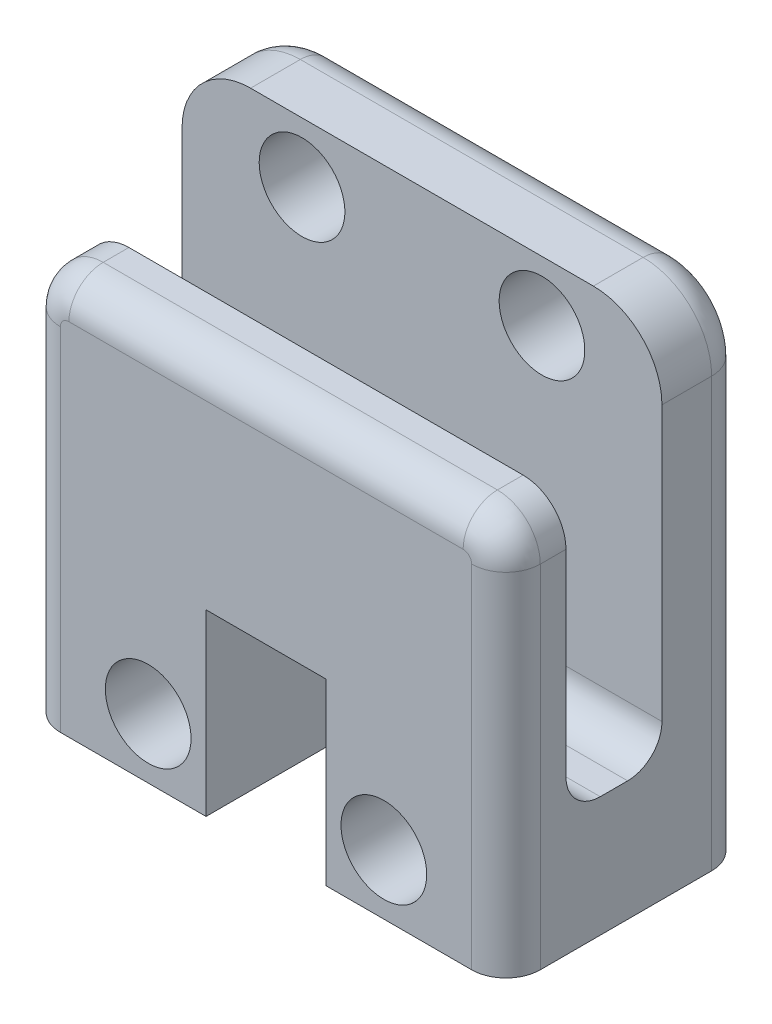
SolidWorks part; units mm, degrees
ref_plane "Front" through (0, 0, 0) normal (0, 0, 1) x (1, 0, 0)
ref_plane "Top" through (0, 0, 0) normal (0, 1, 0) x (1, 0, 0)
ref_plane "Right" through (0, 0, 0) normal (1, 0, 0) x (0, 0, -1)
sketch "Sketch1" plane through (0, 0, 0) normal (0, 1, 0) x (1, 0, 0)
  line L0 (0, 0) -> (0, 17.78)
  line L1 (0, 17.78) -> (35.56, 17.78)
  line L2 (35.56, 17.78) -> (35.56, 0)
  line L8 (12.7, 0) -> (0, 0)
  line L9 (22.86, 0) -> (35.56, 0)
  line L15 (12.7, 0) -> (22.86, 0)
  point P0 (36.4977, 25.3605)
  dimension "D1" = 17.78
  dimension "D2" = 10.16
  dimension "D5" = 35.56
extrude "Boss-Extrude1" add sketch "Sketch1" along normal blind 8.89 contours L15 L2 L1 L0 region at (17.78, 0, -8.89)
sketch "Sketch2" plane through (0, 8.89, 0) normal (0, 1, 0) x (1, 0, 0)
  line L0 (0, 0) -> (35.56, 0)
  line L2 (35.56, 0) -> (35.56, 17.78) construction
  line L4 (0, 17.78) -> (35.56, 17.78) construction
  line L5 (0, 0) -> (0, 17.78)
  line L6 (35.56, 0) -> (35.56, 17.78)
  line L7 (0, 17.78) -> (35.56, 17.78)
  line L8 (0, 0) -> (35.56, 0) construction
  point P3 (17.78, 0)
  dimension "D1" = 17.78
extrude "Boss-Extrude2" add sketch "Sketch2" along normal blind 27.94
sketch "Sketch4" plane through (0, 36.83, 0) normal (0, 1, 0) x (1, 0, 0)
  line L0 (0, 11.557) -> (35.56, 11.557)
  line L1 (0, 17.78) -> (0, 0) construction
  line L2 (35.56, 0) -> (35.56, 17.78) construction
  line L3 (0, 4.445) -> (35.56, 4.445)
  line L4 (0, 11.557) -> (0, 4.445)
  line L5 (35.56, 11.557) -> (35.56, 4.445)
  line L6 (0, 0) -> (35.56, 0) construction
  dimension "D1" = 7.112
  dimension "D2" = 4.445
extrude "Cut-Extrude2" cut sketch "Sketch4" against normal blind 27.94
sketch "Sketch5" plane through (0, 36.83, 0) normal (0, 1, 0) x (1, 0, 0)
  line L0 (35.56, 0) -> (35.56, 4.445) construction
  line L1 (0, 0) -> (35.56, 0) construction
  line L2 (0, 4.445) -> (0, 0) construction
  line L3 (0, 4.445) -> (35.56, 4.445) construction
  line L4 (35.56, 0) -> (35.56, 4.445)
  line L5 (0, 0) -> (35.56, 0)
  line L6 (0, 4.445) -> (0, 0)
  line L7 (0, 4.445) -> (35.56, 4.445)
extrude "Cut-Extrude3" cut sketch "Sketch5" against normal blind 7.62
sketch "Sketch6" plane through (0, 0, -17.78) normal (0, 0, -1) x (-1, 0, 0)
  line L0 (-17.78, 36.83) -> (-17.78, 20.6523) construction
  line L1 (-35.56, 36.83) -> (0, 36.83) construction
  line L2 (-17.78, 32.385) -> (0, 32.385) construction
  line L3 (0, 36.83) -> (0, 0) construction
  circle A0 centre (-8.89, 32.385) radius 3.175
  circle A1 centre (-26.67, 32.385) radius 3.175
  point P2 (-14.1718, 32.385)
  point P11 (-8.89, 32.385)
  dimension "D1" = 6.35
  dimension "D2" = 4.445
extrude "Cut-Extrude4" cut sketch "Sketch6" against normal blind 6.35
sketch "Sketch7" plane through (0, 0, 0) normal (0, 0, 1) x (1, 0, 0)
  line L0 (35.56, 0) -> (0, 0) construction
  line L4 (17.78, 0) -> (17.78, 10.1718) construction
  line L5 (0, 0) -> (35.56, 0) construction
  circle A0 centre (26.5112, 4.445) radius 3.175
  circle A1 centre (9.0487, 4.445) radius 3.175
  dimension "D1" = 6.35
  dimension "D2" = 4.445
  dimension "D3" = 17.4625
extrude "Cut-Extrude5" cut sketch "Sketch7" against normal blind 9.525
fillet "Fillet2" radius 3.175 2 edges at (35.56, 29.21, -2.2225) (0, 29.21, -2.2225)
fillet "Fillet8" radius 5.08 2 edges at (35.56, 36.83, -14.6685) (0, 36.83, -14.6685)
sketch "Sketch8" [suppressed] plane through (0, 8.89, 0) normal (0, 1, 0) x (1, 0, 0)
  line L0 (12.7, 7.62) -> (22.86, 7.62)
  line L1 (22.86, 7.62) -> (22.86, 0)
  line L2 (22.86, 0) -> (31.75, 0)
  line L3 (31.75, 0) -> (31.75, -8.89)
  line L4 (31.75, -8.89) -> (3.81, -8.89)
  line L5 (3.81, -8.89) -> (3.81, 0)
  line L6 (3.81, 0) -> (12.7, 0)
  line L7 (12.7, 0) -> (12.7, 7.62)
extrude "Boss-Extrude3" [suppressed] add sketch "Sketch8" against normal up to surface (8.89 mm away) up to face at (17.78, 0, -8.89)
sketch "Sketch9" [suppressed] plane through (0, 0, 0) normal (0, -1, 0) x (1, 0, 0)
  line L0 (0, 2.54) -> (35.56, 2.54)
  line L1 (0, 8.89) -> (0, -25.4) construction
  line L2 (35.56, 8.89) -> (35.56, -25.4) construction
  line L3 (35.56, 8.89) -> (0, 8.89) construction
  line L4 (0, 8.89) -> (0, 2.54)
  line L5 (35.56, 8.89) -> (35.56, 2.54)
  line L6 (35.56, 8.89) -> (0, 8.89)
  dimension "D1" = 6.35
extrude "Boss-Extrude4" [suppressed] add sketch "Sketch9" along normal blind 25.4
sketch "Sketch10" [suppressed] plane through (0, 0, 8.89) normal (0, 0, 1) x (1, 0, 0)
  line L0 (0, 0) -> (35.56, 0) construction
  line L1 (35.56, 7.62) -> (35.56, -25.4) construction
  line L2 (17.78, 0) -> (17.78, -25.4) construction
  line L3 (35.56, -25.4) -> (0, -25.4) construction
  line L4 (5.08, -12.7) -> (30.48, -12.7) construction
  circle A0 centre (5.08, -12.7) radius 2.5781
  circle A1 centre (17.78, -12.7) radius 1.5827
  circle A2 centre (30.48, -12.7) radius 1.2748
  point P12 (17.78, -12.7)
  point P13 (17.78, -12.7)
  dimension "D2" = 5.1562
  dimension "D1" = 25.4
sketch "Sketch11" [suppressed] plane through (0, 8.89, 0) normal (0, 1, 0) x (1, 0, 0)
  line L0 (0, -2.54) -> (35.56, -2.54)
  line L1 (0, -8.89) -> (0, 7.62) construction
  line L2 (35.56, -8.89) -> (35.56, 7.62) construction
  line L3 (0, -8.89) -> (35.56, -8.89) construction
  line L4 (35.56, -8.89) -> (35.56, -2.54)
  line L5 (0, -8.89) -> (35.56, -8.89)
  line L6 (0, -8.89) -> (0, -2.54)
  dimension "D1" = 6.35
extrude "Cut-Extrude6" [suppressed] cut sketch "Sketch11" against normal through all
sketch "Sketch12" [suppressed] plane through (0, 0, 2.54) normal (0, 0, 1) x (1, 0, 0)
  line L0 (17.78, 8.89) -> (17.78, 0) construction
  line L1 (35.56, 8.89) -> (0, 8.89) construction
  line L2 (35.56, 0) -> (0, 0) construction
  line L3 (17.78, 4.445) -> (0, 4.445) construction
  line L4 (0, 0) -> (0, 8.89) construction
  line L5 (17.78, 4.445) -> (35.56, 4.445) construction
  line L6 (35.56, 0) -> (35.56, 8.89) construction
  circle A0 centre (8.89, 4.445) radius 3.175
  circle A1 centre (26.67, 4.445) radius 3.175
  dimension "D1" = 6.35
extrude "Cut-Extrude7" [suppressed] cut sketch "Sketch12" against normal blind 7.62
fillet "Fillet4" [suppressed] radius 3.175
fillet "Fillet6" radius 2.54 2 edges at (17.78, 8.89, -4.445) (17.78, 8.89, -11.557)
sketch "Sketch15" plane through (0, 0, 0) normal (0, 0, 1) x (1, 0, 0)
  line L0 (13.335, 0) -> (13.335, 10.16)
  line L1 (35.56, 0) -> (0, 0) construction
  line L2 (13.335, 10.16) -> (22.225, 10.16)
  line L3 (22.225, 10.16) -> (22.225, 0)
  line L4 (22.225, 0) -> (13.335, 0)
  point P4 (17.78, 0)
  point P7 (17.78, 10.16)
  dimension "D1" = 8.89
  dimension "D2" = 10.16
revolve "Cut-Revolve1" cut sketch "Sketch15" angle 360 about L4
fillet "Fillet9" radius 2.54 10 edges at (0, 13.0175, 0) (0.9299, 28.2801, 0) (35.56, 13.0175, 0) (34.6301, 28.2801, 0) (17.78, 29.21, 0) (35.56, 15.875, -17.78) (34.0721, 35.3421, -17.78) (0, 15.875, -17.78) (1.4879, 35.3421, -17.78) (17.78, 36.83, -17.78)
sketch "Sketch16" plane through (22.225, 0, 0) normal (-1, 0, 0) x (0, 0, 1)
  line L1 (0, 13.2629) -> (-6.5307, 7.783)
  line L2 (0, 0) -> (0, 10.16)
  line L3 (-10.16, 0) -> (0, 0)
  line L4 (0, 0) -> (0, 13.2629)
  line L5 (-10.16, 0) -> (0, 0)
  arc A1 (0, 10.16) -> (-10.16, 0) centre (0, 0) ccw
  arc A2 (-6.5307, 7.783) -> (-10.16, 0) centre (0, 0) ccw
  dimension "D2" = 40
  dimension "D1" = 0
extrude "Cut-Extrude9" cut sketch "Sketch16" along normal up to surface (8.89 mm away) up to face at (13.335, 4.0881, -4.0881)
sketch "Sketch14" [suppressed] plane through (0, 0, 0) normal (0, 0, 1) x (1, 0, 0)
  line L0 (12.7, 6.985) -> (8.255, 6.985) construction
  line L1 (12.7, 24.13) -> (12.7, 3.175) construction
  line L2 (8.255, 0) -> (8.255, 6.985) construction
  line L3 (12.7, 0) -> (0, 0) construction
  line L4 (12.7, 24.13) -> (22.86, 24.13) construction
  line L5 (17.78, 24.13) -> (17.78, 5.5416) construction
  line L6 (27.305, 0) -> (27.305, 6.985) construction
  line L7 (22.86, 6.985) -> (27.305, 6.985) construction
  circle A0 centre (8.255, 6.985) radius 3.175
  circle A1 centre (27.305, 6.985) radius 3.175
  dimension "D3" = 6.35
  dimension "D1" = 4.445
  dimension "D2" = 6.985
extrude "Cut-Extrude8" [suppressed] cut sketch "Sketch14" against normal blind 9.525
